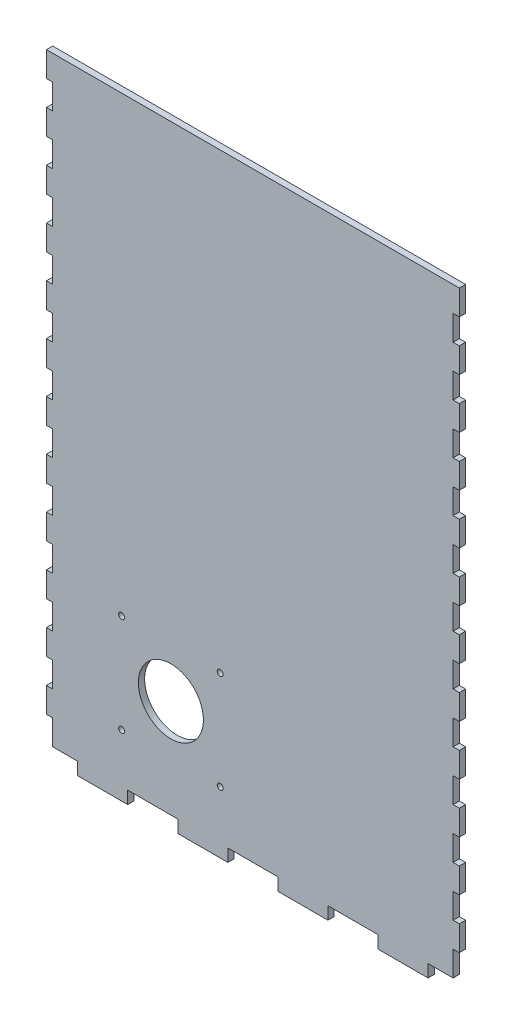
SolidWorks part; units mm, degrees
ref_plane "Front Plane" through (0, 0, 0) normal (0, 0, 1) x (1, 0, 0)
ref_plane "Top Plane" through (0, 0, 0) normal (0, 1, 0) x (1, 0, 0)
ref_plane "Right Plane" through (0, 0, 0) normal (1, 0, 0) x (0, 0, -1)
sketch "Sketch1" plane through (0, 0, 0) normal (0, 0, 1) x (1, 0, 0)
  line L0 (0, 0) -> (203.2, 0)
  line L1 (203.2, 0) -> (203.2, 304.8)
  line L2 (203.2, 304.8) -> (0, 304.8)
  line L3 (0, 304.8) -> (0, 0)
  dimension "D1" = 203.2
  dimension "D2" = 304.8
extrude "Boss-Extrude1" add sketch "Sketch1" along normal blind 3.175
sketch "Sketch2" plane through (0, 0, 3.175) normal (0, 0, 1) x (1, 0, 0)
  line L0 (0, 304.8) -> (-3.175, 304.8)
  line L1 (-3.175, 304.8) -> (-3.175, 292.1)
  line L2 (-3.175, 292.1) -> (0, 292.1)
  line L3 (0, 304.8) -> (0, 0) construction
  line L4 (0, 292.1) -> (0, 304.8)
  line L5 (101.6, 304.8) -> (101.6, 0) construction
  line L6 (203.2, 304.8) -> (0, 304.8) construction
  line L7 (0, 0) -> (203.2, 0) construction
  line L8 (206.375, 292.1) -> (203.2, 292.1)
  line L9 (206.375, 304.8) -> (206.375, 292.1)
  line L10 (203.2, 304.8) -> (206.375, 304.8)
  line L11 (203.2, 292.1) -> (203.2, 304.8)
  line L12 (0, 266.7) -> (0, 279.4)
  line L13 (0, 279.4) -> (-3.175, 279.4)
  line L14 (-3.175, 279.4) -> (-3.175, 266.7)
  line L15 (-3.175, 266.7) -> (0, 266.7)
  line L16 (206.375, 266.7) -> (203.2, 266.7)
  line L17 (203.2, 266.7) -> (203.2, 279.4)
  line L18 (203.2, 279.4) -> (206.375, 279.4)
  line L19 (206.375, 279.4) -> (206.375, 266.7)
  line L20 (0, 241.3) -> (0, 254)
  line L21 (0, 254) -> (-3.175, 254)
  line L22 (-3.175, 254) -> (-3.175, 241.3)
  line L23 (-3.175, 241.3) -> (0, 241.3)
  line L24 (206.375, 241.3) -> (203.2, 241.3)
  line L25 (203.2, 241.3) -> (203.2, 254)
  line L26 (203.2, 254) -> (206.375, 254)
  line L27 (206.375, 254) -> (206.375, 241.3)
  line L28 (0, 215.9) -> (0, 228.6)
  line L29 (0, 228.6) -> (-3.175, 228.6)
  line L30 (-3.175, 228.6) -> (-3.175, 215.9)
  line L31 (-3.175, 215.9) -> (0, 215.9)
  line L32 (206.375, 215.9) -> (203.2, 215.9)
  line L33 (203.2, 215.9) -> (203.2, 228.6)
  line L34 (203.2, 228.6) -> (206.375, 228.6)
  line L35 (206.375, 228.6) -> (206.375, 215.9)
  line L36 (0, 190.5) -> (0, 203.2)
  line L37 (0, 203.2) -> (-3.175, 203.2)
  line L38 (-3.175, 203.2) -> (-3.175, 190.5)
  line L39 (-3.175, 190.5) -> (0, 190.5)
  line L40 (206.375, 190.5) -> (203.2, 190.5)
  line L41 (203.2, 190.5) -> (203.2, 203.2)
  line L42 (203.2, 203.2) -> (206.375, 203.2)
  line L43 (206.375, 203.2) -> (206.375, 190.5)
  line L44 (0, 165.1) -> (0, 177.8)
  line L45 (0, 177.8) -> (-3.175, 177.8)
  line L46 (-3.175, 177.8) -> (-3.175, 165.1)
  line L47 (-3.175, 165.1) -> (0, 165.1)
  line L48 (206.375, 165.1) -> (203.2, 165.1)
  line L49 (203.2, 165.1) -> (203.2, 177.8)
  line L50 (203.2, 177.8) -> (206.375, 177.8)
  line L51 (206.375, 177.8) -> (206.375, 165.1)
  line L52 (0, 139.7) -> (0, 152.4)
  line L53 (0, 152.4) -> (-3.175, 152.4)
  line L54 (-3.175, 152.4) -> (-3.175, 139.7)
  line L55 (-3.175, 139.7) -> (0, 139.7)
  line L56 (206.375, 139.7) -> (203.2, 139.7)
  line L57 (203.2, 139.7) -> (203.2, 152.4)
  line L58 (203.2, 152.4) -> (206.375, 152.4)
  line L59 (206.375, 152.4) -> (206.375, 139.7)
  line L60 (0, 114.3) -> (0, 127)
  line L61 (0, 127) -> (-3.175, 127)
  line L62 (-3.175, 127) -> (-3.175, 114.3)
  line L63 (-3.175, 114.3) -> (0, 114.3)
  line L64 (206.375, 114.3) -> (203.2, 114.3)
  line L65 (203.2, 114.3) -> (203.2, 127)
  line L66 (203.2, 127) -> (206.375, 127)
  line L67 (206.375, 127) -> (206.375, 114.3)
  line L68 (0, 88.9) -> (0, 101.6)
  line L69 (0, 101.6) -> (-3.175, 101.6)
  line L70 (-3.175, 101.6) -> (-3.175, 88.9)
  line L71 (-3.175, 88.9) -> (0, 88.9)
  line L72 (206.375, 88.9) -> (203.2, 88.9)
  line L73 (203.2, 88.9) -> (203.2, 101.6)
  line L74 (203.2, 101.6) -> (206.375, 101.6)
  line L75 (206.375, 101.6) -> (206.375, 88.9)
  line L76 (0, 63.5) -> (0, 76.2)
  line L77 (0, 76.2) -> (-3.175, 76.2)
  line L78 (-3.175, 76.2) -> (-3.175, 63.5)
  line L79 (-3.175, 63.5) -> (0, 63.5)
  line L80 (206.375, 63.5) -> (203.2, 63.5)
  line L81 (203.2, 63.5) -> (203.2, 76.2)
  line L82 (203.2, 76.2) -> (206.375, 76.2)
  line L83 (206.375, 76.2) -> (206.375, 63.5)
  line L84 (0, 38.1) -> (0, 50.8)
  line L85 (0, 50.8) -> (-3.175, 50.8)
  line L86 (-3.175, 50.8) -> (-3.175, 38.1)
  line L87 (-3.175, 38.1) -> (0, 38.1)
  line L88 (206.375, 38.1) -> (203.2, 38.1)
  line L89 (203.2, 38.1) -> (203.2, 50.8)
  line L90 (203.2, 50.8) -> (206.375, 50.8)
  line L91 (206.375, 50.8) -> (206.375, 38.1)
  line L92 (0, 12.7) -> (0, 25.4)
  line L93 (0, 25.4) -> (-3.175, 25.4)
  line L94 (-3.175, 25.4) -> (-3.175, 12.7)
  line L95 (-3.175, 12.7) -> (0, 12.7)
  line L96 (206.375, 12.7) -> (203.2, 12.7)
  line L97 (203.2, 12.7) -> (203.2, 25.4)
  line L98 (203.2, 25.4) -> (206.375, 25.4)
  line L99 (206.375, 25.4) -> (206.375, 12.7)
  line L100 (0, 292.1) -> (0, 266.7) construction
  line L101 (12.7, 0) -> (12.7, -6.35)
  line L102 (12.7, -6.35) -> (38.1, -6.35)
  line L103 (38.1, -6.35) -> (38.1, 0)
  line L104 (38.1, 0) -> (12.7, 0)
  line L105 (88.9, 0) -> (63.5, 0)
  line L106 (63.5, 0) -> (63.5, -6.35)
  line L107 (63.5, -6.35) -> (88.9, -6.35)
  line L108 (88.9, -6.35) -> (88.9, 0)
  line L109 (139.7, 0) -> (114.3, 0)
  line L110 (114.3, 0) -> (114.3, -6.35)
  line L111 (114.3, -6.35) -> (139.7, -6.35)
  line L112 (139.7, -6.35) -> (139.7, 0)
  line L113 (190.5, 0) -> (165.1, 0)
  line L114 (165.1, 0) -> (165.1, -6.35)
  line L115 (165.1, -6.35) -> (190.5, -6.35)
  line L116 (190.5, -6.35) -> (190.5, 0)
  line L117 (38.1, 0) -> (88.9, 0) construction
  dimension "D1" = 3.175
  dimension "D2" = 12.7
  dimension "D4" = 25.4
  dimension "D5" = 12.7
  dimension "D6" = 6.35
  dimension "D7" = 25.4
  dimension "D9" = 50.8
  dimension "D3" = 12
  dimension "D8" = 4
extrude "Boss-Extrude2" add sketch "Sketch2" against normal up to surface (3.175 mm away) up to face at (101.6, 152.4, 0)
sketch "Sketch3" [suppressed] plane through (0, 0, 3.175) normal (0, 0, 1) x (1, 0, 0)
  line L0 (0, 0) -> (-3.175, 0)
  line L1 (-3.175, 0) -> (-3.175, 12.7)
  line L2 (-3.175, 12.7) -> (0, 12.7)
  line L3 (0, 304.8) -> (0, 0) construction
  line L4 (0, 12.7) -> (0, 0)
  line L5 (101.6, 304.8) -> (101.6, 0) construction
  line L6 (203.2, 304.8) -> (0, 304.8) construction
  line L7 (0, 0) -> (203.2, 0) construction
  line L8 (206.375, 12.7) -> (203.2, 12.7)
  line L9 (206.375, 0) -> (206.375, 12.7)
  line L10 (203.2, 0) -> (206.375, 0)
  line L11 (203.2, 12.7) -> (203.2, 0)
  line L12 (0, 38.1) -> (0, 25.4)
  line L13 (0, 25.4) -> (-3.175, 25.4)
  line L14 (-3.175, 25.4) -> (-3.175, 38.1)
  line L15 (-3.175, 38.1) -> (0, 38.1)
  line L16 (206.375, 38.1) -> (203.2, 38.1)
  line L17 (203.2, 38.1) -> (203.2, 25.4)
  line L18 (203.2, 25.4) -> (206.375, 25.4)
  line L19 (206.375, 25.4) -> (206.375, 38.1)
  line L20 (0, 63.5) -> (0, 50.8)
  line L21 (0, 50.8) -> (-3.175, 50.8)
  line L22 (-3.175, 50.8) -> (-3.175, 63.5)
  line L23 (-3.175, 63.5) -> (0, 63.5)
  line L24 (206.375, 63.5) -> (203.2, 63.5)
  line L25 (203.2, 63.5) -> (203.2, 50.8)
  line L26 (203.2, 50.8) -> (206.375, 50.8)
  line L27 (206.375, 50.8) -> (206.375, 63.5)
  line L28 (0, 88.9) -> (0, 76.2)
  line L29 (0, 76.2) -> (-3.175, 76.2)
  line L30 (-3.175, 76.2) -> (-3.175, 88.9)
  line L31 (-3.175, 88.9) -> (0, 88.9)
  line L32 (206.375, 88.9) -> (203.2, 88.9)
  line L33 (203.2, 88.9) -> (203.2, 76.2)
  line L34 (203.2, 76.2) -> (206.375, 76.2)
  line L35 (206.375, 76.2) -> (206.375, 88.9)
  line L36 (0, 114.3) -> (0, 101.6)
  line L37 (0, 101.6) -> (-3.175, 101.6)
  line L38 (-3.175, 101.6) -> (-3.175, 114.3)
  line L39 (-3.175, 114.3) -> (0, 114.3)
  line L40 (206.375, 114.3) -> (203.2, 114.3)
  line L41 (203.2, 114.3) -> (203.2, 101.6)
  line L42 (203.2, 101.6) -> (206.375, 101.6)
  line L43 (206.375, 101.6) -> (206.375, 114.3)
  line L44 (0, 139.7) -> (0, 127)
  line L45 (0, 127) -> (-3.175, 127)
  line L46 (-3.175, 127) -> (-3.175, 139.7)
  line L47 (-3.175, 139.7) -> (0, 139.7)
  line L48 (206.375, 139.7) -> (203.2, 139.7)
  line L49 (203.2, 139.7) -> (203.2, 127)
  line L50 (203.2, 127) -> (206.375, 127)
  line L51 (206.375, 127) -> (206.375, 139.7)
  line L52 (0, 165.1) -> (0, 152.4)
  line L53 (0, 152.4) -> (-3.175, 152.4)
  line L54 (-3.175, 152.4) -> (-3.175, 165.1)
  line L55 (-3.175, 165.1) -> (0, 165.1)
  line L56 (206.375, 165.1) -> (203.2, 165.1)
  line L57 (203.2, 165.1) -> (203.2, 152.4)
  line L58 (203.2, 152.4) -> (206.375, 152.4)
  line L59 (206.375, 152.4) -> (206.375, 165.1)
  line L60 (0, 190.5) -> (0, 177.8)
  line L61 (0, 177.8) -> (-3.175, 177.8)
  line L62 (-3.175, 177.8) -> (-3.175, 190.5)
  line L63 (-3.175, 190.5) -> (0, 190.5)
  line L64 (206.375, 190.5) -> (203.2, 190.5)
  line L65 (203.2, 190.5) -> (203.2, 177.8)
  line L66 (203.2, 177.8) -> (206.375, 177.8)
  line L67 (206.375, 177.8) -> (206.375, 190.5)
  line L68 (0, 215.9) -> (0, 203.2)
  line L69 (0, 203.2) -> (-3.175, 203.2)
  line L70 (-3.175, 203.2) -> (-3.175, 215.9)
  line L71 (-3.175, 215.9) -> (0, 215.9)
  line L72 (206.375, 215.9) -> (203.2, 215.9)
  line L73 (203.2, 215.9) -> (203.2, 203.2)
  line L74 (203.2, 203.2) -> (206.375, 203.2)
  line L75 (206.375, 203.2) -> (206.375, 215.9)
  line L76 (0, 241.3) -> (0, 228.6)
  line L77 (0, 228.6) -> (-3.175, 228.6)
  line L78 (-3.175, 228.6) -> (-3.175, 241.3)
  line L79 (-3.175, 241.3) -> (0, 241.3)
  line L80 (206.375, 241.3) -> (203.2, 241.3)
  line L81 (203.2, 241.3) -> (203.2, 228.6)
  line L82 (203.2, 228.6) -> (206.375, 228.6)
  line L83 (206.375, 228.6) -> (206.375, 241.3)
  line L84 (0, 266.7) -> (0, 254)
  line L85 (0, 254) -> (-3.175, 254)
  line L86 (-3.175, 254) -> (-3.175, 266.7)
  line L87 (-3.175, 266.7) -> (0, 266.7)
  line L88 (206.375, 266.7) -> (203.2, 266.7)
  line L89 (203.2, 266.7) -> (203.2, 254)
  line L90 (203.2, 254) -> (206.375, 254)
  line L91 (206.375, 254) -> (206.375, 266.7)
  line L92 (0, 292.1) -> (0, 279.4)
  line L93 (0, 279.4) -> (-3.175, 279.4)
  line L94 (-3.175, 279.4) -> (-3.175, 292.1)
  line L95 (-3.175, 292.1) -> (0, 292.1)
  line L96 (206.375, 292.1) -> (203.2, 292.1)
  line L97 (203.2, 292.1) -> (203.2, 279.4)
  line L98 (203.2, 279.4) -> (206.375, 279.4)
  line L99 (206.375, 279.4) -> (206.375, 292.1)
  line L100 (0, 12.7) -> (0, 38.1) construction
  line L101 (12.7, 0) -> (12.7, -6.35)
  line L102 (12.7, -6.35) -> (38.1, -6.35)
  line L103 (38.1, -6.35) -> (38.1, 0)
  line L104 (38.1, 0) -> (12.7, 0)
  line L105 (88.9, 0) -> (63.5, 0)
  line L106 (63.5, 0) -> (63.5, -6.35)
  line L107 (63.5, -6.35) -> (88.9, -6.35)
  line L108 (88.9, -6.35) -> (88.9, 0)
  line L109 (139.7, 0) -> (114.3, 0)
  line L110 (114.3, 0) -> (114.3, -6.35)
  line L111 (114.3, -6.35) -> (139.7, -6.35)
  line L112 (139.7, -6.35) -> (139.7, 0)
  line L113 (190.5, 0) -> (165.1, 0)
  line L114 (165.1, 0) -> (165.1, -6.35)
  line L115 (165.1, -6.35) -> (190.5, -6.35)
  line L116 (190.5, -6.35) -> (190.5, 0)
  line L117 (38.1, 0) -> (88.9, 0) construction
  dimension "D1" = 3.175
  dimension "D2" = 12.7
  dimension "D9" = 50.8
  dimension "D3" = 12
  dimension "D8" = 4
  dimension "D4" = 25.4
  dimension "D5" = 6.35
  dimension "D6" = 25.4
  dimension "D7" = 12.7
extrude "Boss-Extrude3" [suppressed] add sketch "Sketch3" against normal up to surface (3.175 mm away) up to face at (101.6, 130.175, 0)
sketch "Sketch4" plane through (0, 0, 3.175) normal (0, 0, 1) x (1, 0, 0)
  line L0 (60, 33.5) -> (60, 66.5) construction
  line L1 (43.5, 50) -> (76.5, 50) construction
  line L2 (0, 12.7) -> (0, 0) construction
  line L3 (88.9, 0) -> (114.3, 0) construction
  circle A0 centre (60, 50) radius 16.5
  circle A1 centre (35, 75) radius 1.5
  circle A5 centre (85, 75) radius 1.5
  circle A6 centre (85, 25) radius 1.5
  circle A7 centre (35, 25) radius 1.5
  dimension "D5" = 33
  dimension "D6" = 3
  dimension "D1" = 50
  dimension "D2" = 50
  dimension "D3" = 60
  dimension "D4" = 50
extrude "Cut-Extrude1" cut sketch "Sketch4" against normal up to surface (3.175 mm away) up to face at (101.6, 130.175, 0)
equation "\"wall_thickness\" = 0.125in"
equation "\"base_thickness\" = 0.25in"
equation "\"D1@Boss-Extrude1\"=\"wall_thickness\""
equation "\"D1@Sketch2\"=\"wall_thickness\""
equation "\"D6@Sketch2\"=\"base_thickness\""
equation "\"D1@Sketch3\"=\"wall_thickness\""
equation "\"D5@Sketch3\"=\"base_thickness\""
